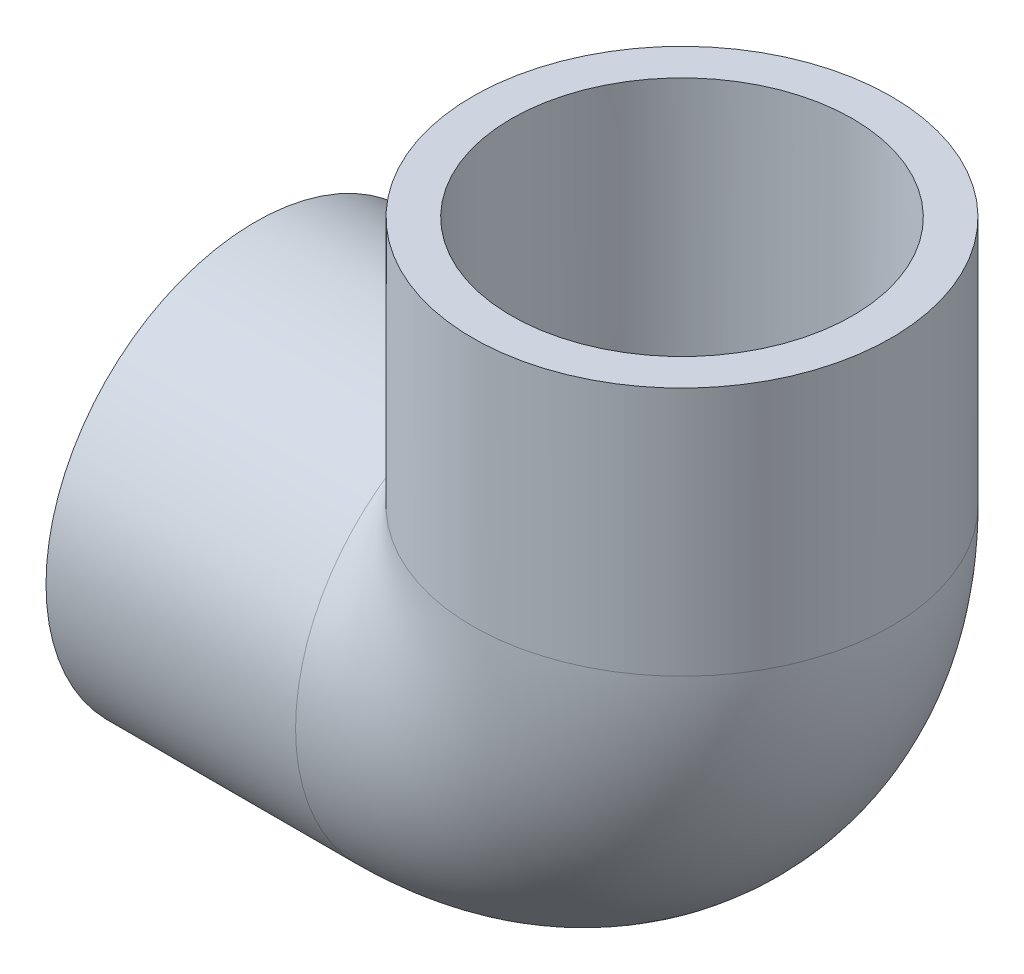
SolidWorks part; units mm, degrees
ref_plane "Front Plane" through (0, 0, 0) normal (0, 0, 1) x (1, 0, 0)
ref_plane "Top Plane" through (0, 0, 0) normal (0, 1, 0) x (1, 0, 0)
ref_plane "Right Plane" through (0, 0, 0) normal (1, 0, 0) x (0, 0, -1)
sketch "Sketch0" plane through (0, 0, 0) normal (0, 0, 1) x (1, 0, 0)
  line L0 (-42.0688, 0) -> (0, 0) construction
  line L1 (0, 0) -> (0, 42.0688) construction
  line L2 (-17.4625, 0) -> (0, 0) construction
  line L3 (0, 0) -> (0, 17.4625) construction
  line L4 (-42.0687, 20.6375) -> (-42.0687, -20.6375) construction
  line L5 (-17.4625, 16.637) -> (-42.0687, 16.8275) construction
  line L6 (-17.4625, 16.637) -> (-17.4625, -16.637) construction
  line L7 (-17.4625, -16.637) -> (-42.0687, -16.8275) construction
  line L8 (-42.0687, 16.8275) -> (-42.0687, -16.8275) construction
  line L9 (-20.6375, 42.0688) -> (20.6375, 42.0688) construction
  line L10 (-16.8275, 42.0688) -> (16.8275, 42.0688) construction
  line L11 (16.8275, 42.0688) -> (16.637, 17.4625) construction
  line L12 (16.637, 17.4625) -> (-16.637, 17.4625) construction
  line L13 (-16.637, 17.4625) -> (-16.8275, 42.0688) construction
  line L14 (-17.4625, 13.3223) -> (-17.4625, -13.3223) construction
  line L18 (-13.3223, 17.4625) -> (13.3223, 17.4625) construction
  dimension "H" = 42.0688
  dimension "G" = 17.4625
  dimension "M" = 41.275
  dimension "OD A" = 33.655
  dimension "OD B" = 33.274
  dimension "ID" = 26.6446
sketch "Sketch1" plane through (0, 0, 0) normal (0, 0, 1) x (1, 0, 0)
  line L0 (-42.0688, 0) -> (0, 0) construction
  line L1 (-42.0688, 0) -> (0, 0) construction
  line L3 (-42.0687, -20.6375) -> (-17.4625, -20.6375)
  line L4 (-42.0687, -20.6375) -> (-42.0687, -16.8275)
  line L5 (-42.0687, -16.8275) -> (-17.4625, -16.637)
  line L6 (-17.4625, -20.6375) -> (-17.4625, -16.637)
revolve "Revolve1" add sketch "Sketch1" angle 360 about L1
sketch "Sketch2" plane through (0, 0, 0) normal (0, 0, 1) x (1, 0, 0)
  line L0 (16.8275, 42.0688) -> (16.637, 17.4625)
  line L1 (16.637, 17.4625) -> (20.6375, 17.4625)
  line L2 (20.6375, 17.4625) -> (20.6375, 42.0688)
  line L3 (20.6375, 42.0688) -> (16.8275, 42.0688)
  line L4 (0, 0) -> (0, 42.0688) construction
  line L5 (0, 0) -> (0, 42.0688) construction
revolve "Revolve2" add sketch "Sketch2" angle 360 about L5
sketch "Sketch3" plane through (-17.4625, 0, 0) normal (1, 0, 0) x (0, 0, -1)
  circle A0 centre (0, 0) radius 13.3223
  circle A1 centre (0, 0) radius 20.6375
sketch "Sketch4" plane through (0, 0, 0) normal (0, 0, 1) x (1, 0, 0)
  line L0 (-42.0688, 0) -> (0, 0) construction
  line L1 (0, 0) -> (0, 42.0688) construction
  line L2 (-42.0688, 0) -> (-17.4625, 0) construction
  line L3 (0, 17.4625) -> (0, 42.0688) construction
  arc A0 (-17.4625, 0) -> (0, 17.4625) centre (-17.4625, 17.4625) ccw
sweep "Sweep1" add profiles "Sketch3" path "Sketch4"
